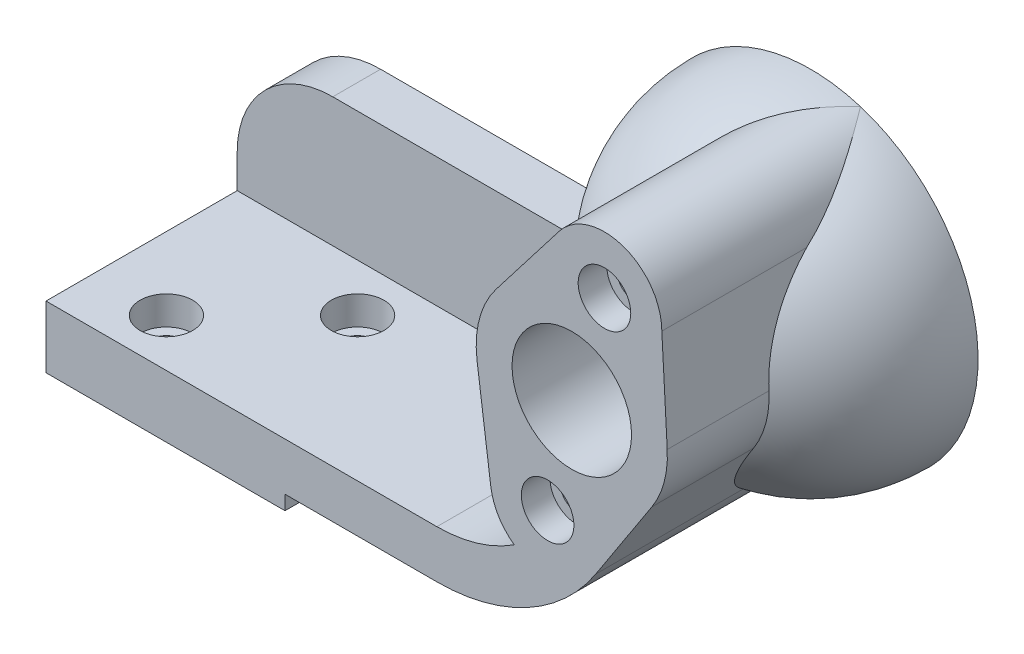
SolidWorks part; units mm, degrees
ref_plane "Front Plane" through (0, 0, 0) normal (0, 0, 1) x (1, 0, 0)
ref_plane "Top Plane" through (0, 0, 0) normal (0, 1, 0) x (1, 0, 0)
ref_plane "Right Plane" through (0, 0, 0) normal (1, 0, 0) x (0, 0, -1)
sketch "Sketch1" plane through (0, 0, 0) normal (0, 0, 1) x (1, 0, 0)
  line L0 (0, 0) -> (50, 0)
  line L1 (50, 0) -> (50, 3)
  line L2 (50, 3) -> (81.7759, 3)
  line L4 (81.7759, 13) -> (0, 13)
  line L5 (0, 13) -> (0, 0)
  line L8 (93.0489, 25.9654) -> (90.178, 47.3373)
  line L9 (114.9995, 21.0172) -> (126.7624, 39.0902)
  line L10 (107.3372, 79.2901) -> (94.165, 62.2169)
  line L11 (128.8382, 71.9599) -> (129.9706, 51.0833)
  circle A0 centre (110, 50) radius 12.5
  circle A2 centre (116.8382, 71.9599) radius 5.5
  circle A3 centre (104.9421, 27.563) radius 5.5
  arc A4 (94.165, 62.2169) -> (90.178, 47.3373) centre (110, 50) ccw
  arc A8 (126.7624, 39.0902) -> (129.9706, 51.0833) centre (110, 50) ccw
  arc A9 (93.0489, 25.9654) -> (97.9564, 17.806) centre (104.9421, 27.563) ccw
  arc A10 (114.9995, 21.0172) -> (81.7759, 3) centre (81.7759, 42.6407) cw
  arc A11 (128.8382, 71.9599) -> (107.3372, 79.2901) centre (116.8382, 71.9599) ccw
  arc A13 (97.9564, 17.806) -> (81.7759, 13) centre (81.7759, 42.6407) cw
  point P6 (0, 0)
  point P20 (83.661, 36.1021)
  point P22 (86.8301, 3)
  point P29 (114.7365, 20.6297)
  dimension "D4" = 25
  dimension "D8" = 11
  dimension "D9" = 11
  dimension "D12" = 40
  dimension "D1" = 13
  dimension "D2" = 3
  dimension "D3" = 50
  dimension "D6" = 50
  dimension "D7" = 110
  dimension "D11" = 23
extrude "Boss-Extrude1" add sketch "Sketch1" along normal blind 50 contours A3 | A2 | A9 A13 L4 L5 L0 L1 L2 A10 L9 A8 L11 A11 L10 A4 L8 A0 A2 A3 region at (1.5476, 6.5, 0) region at (116.8382, 71.9599, 0) region at (104.9421, 27.563, 0)
sketch "Sketch3" plane through (0, 0, 50) normal (0, 0, 1) x (1, 0, 0)
  circle A0 centre (116.8382, 71.9599) radius 5.5
  circle A1 centre (104.9421, 27.563) radius 5.5
  circle A2 centre (116.8382, 71.9599) radius 3.3
  circle A3 centre (104.9421, 27.563) radius 3.3
  dimension "D1" = 6.6
  dimension "D2" = 6.6
extrude "Cut-Extrude2" cut sketch "Sketch3" against normal blind 6 contours A0 | A1
sketch "Sketch5" plane through (0, 0, 0) normal (0, 0, -1) x (-1, 0, 0)
  line L0 (0, 13) -> (0, 20)
  line L1 (-81.7759, 13) -> (0, 13) construction
  line L2 (-20, 40) -> (-91.1637, 40)
  line L3 (-93.0489, 25.9654) -> (-90.178, 47.3373) construction
  line L4 (-91.1637, 40) -> (-93.0489, 25.9654)
  line L5 (-93.0489, 25.9654) -> (-103.9553, 11.7169)
  line L6 (-103.9553, 11.7169) -> (0, 13)
  arc A0 (-76.459, 40) -> (-100.4189, 16.3369) centre (-110, 50) ccw
  arc A1 (-80.6572, 40) -> (-95.7085, 22.4909) centre (-110, 50) ccw
  arc A2 (0, 20) -> (-20, 40) centre (-20, 20) ccw
  arc M4 (-97.9564, 17.806) -> (-93.0489, 25.9654) centre (-104.9421, 27.563) ccw
  line M5 (-93.0489, 25.9654) -> (-90.178, 47.3373)
  line M17 (0, 13) -> (-81.7759, 13)
  arc M18 (-81.7759, 13) -> (-97.9564, 17.806) centre (-81.7759, 42.6407) cw
  dimension "D1" = 70
  dimension "D2" = 4
  dimension "D3" = 20
  dimension "D4" = 27
extrude "Boss-Extrude2" add sketch "Sketch5" against normal blind 10 contours L0 A2 L2 M5 M4 M18 M17 region at (48.0205, 26.1121, 0)
ref_plane "Plane1" through (110, 0, 0) normal (-1, 0, 0) x (0, 0, 1)
sketch "Sketch6" plane through (110, 0, 0) normal (-1, 0, 0) x (0, 0, 1)
  line L0 (31, 50) -> (35, 50) construction
  line L1 (0, 85) -> (0, 81)
  line L2 (35, 50) -> (31, 50)
  line L3 (35, 50) -> (-21.8468, 50) construction
  line L4 (0, 50) -> (0, 81)
  line L5 (0, 50) -> (35, 50)
  arc A0 (0, 85) -> (35, 50) centre (0, 50) cw
  arc A1 (0, 81) -> (31, 50) centre (0, 50) cw
  dimension "D1" = 35
  dimension "D2" = 4
revolve "Revolve2" add sketch "Sketch6" angle 360 about L3 region at (110, 74.3987, 24.3987) region at (110, 63.1568, 13.1568)
revolve "Cut-Revolve3" cut sketch "Sketch6<5>" angle 360 about L3 region at (110, 63.1568, 13.1568)
sketch "Sketch6<5>" plane through (110, 0, 0) normal (-1, 0, 0) x (0, 0, 1) same geometry as "Sketch6"
sketch "Sketch8" plane through (0, 0, 50) normal (0, 0, 1) x (1, 0, 0)
  circle A0 centre (110, 50) radius 12.5
  circle A1 centre (116.8382, 71.9599) radius 3.3
  circle A2 centre (104.9421, 27.563) radius 3.3
  dimension "D1" = 6.6
  dimension "D2" = 6.6
  dimension "D3" = 25
extrude "Cut-Extrude3" cut sketch "Sketch8" against normal up to next
sketch "Sketch9" plane through (0, 13, 0) normal (0, 1, 0) x (1, 0, 0)
  line L0 (20, 0) -> (76.459, 0) construction
  circle A0 centre (15.1908, -40) radius 5.5
  circle A1 centre (35.1908, -20) radius 5.5
  dimension "D4" = 11
  dimension "D5" = 11
  dimension "D1" = 20
  dimension "D2" = 20
  dimension "D3" = 20
  dimension "D6" = 75
extrude "Cut-Extrude4" cut sketch "Sketch9" against normal blind 6
sketch "Sketch11" plane through (0, 13, 0) normal (0, 1, 0) x (1, 0, 0)
  circle A0 centre (35.1908, -20) radius 3.3
  circle A1 centre (15.1908, -40) radius 3.3
  dimension "D1" = 6.6
  dimension "D2" = 6.6
extrude "Cut-Extrude5" cut sketch "Sketch11" against normal through all
